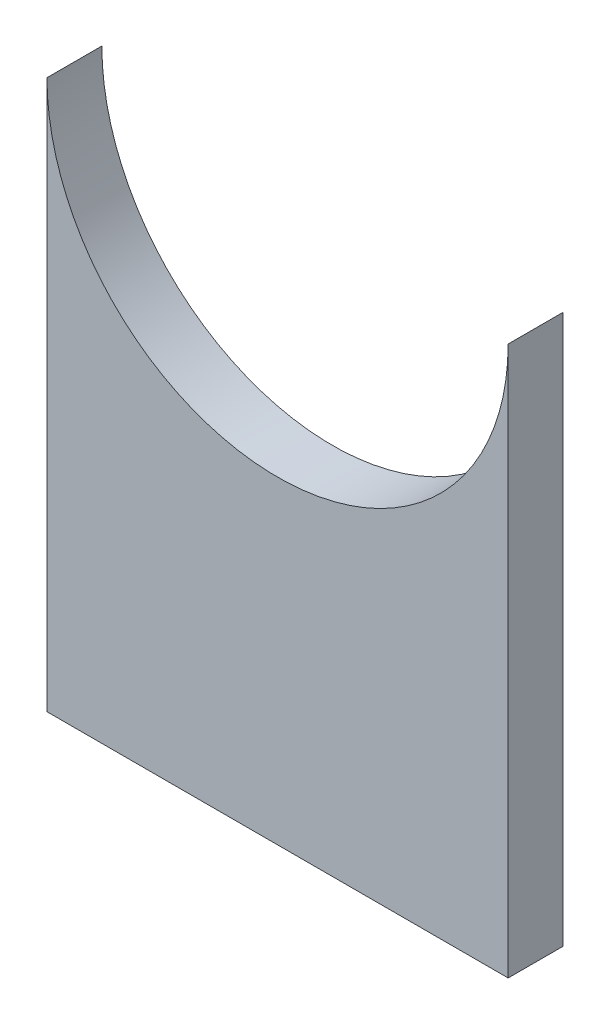
SolidWorks part; units mm, degrees
ref_plane "Front Plane" through (0, 0, 0) normal (0, 0, 1) x (1, 0, 0)
ref_plane "Top Plane" through (0, 0, 0) normal (0, 1, 0) x (1, 0, 0)
ref_plane "Right Plane" through (0, 0, 0) normal (1, 0, 0) x (0, 0, -1)
sketch "Sketch1" plane through (0, 0, 0) normal (0, 0, 1) x (1, 0, 0)
  line L0 (0, -63.5) -> (0, 36.9747) construction
  line L1 (-26.67, -63.5) -> (26.67, -63.5)
  line L2 (-26.67, -63.5) -> (-26.67, 0)
  line L4 (26.67, -63.5) -> (26.67, 0)
  line L5 (-26.67, -63.5) -> (26.67, 0) construction
  line L6 (-26.67, 0) -> (26.67, -63.5) construction
  line L7 (3.937, -50.8) -> (30.2612, -50.8) construction
  arc A0 (-26.67, 0) -> (26.67, 0) centre (0, 0) ccw
  point P3 (0, -31.75)
  dimension "D1" = 63.5
  dimension "D3" = 26.67
  dimension "D2" = 12.7
extrude "Boss-Extrude1" add sketch "Sketch1" along normal blind 6.35
